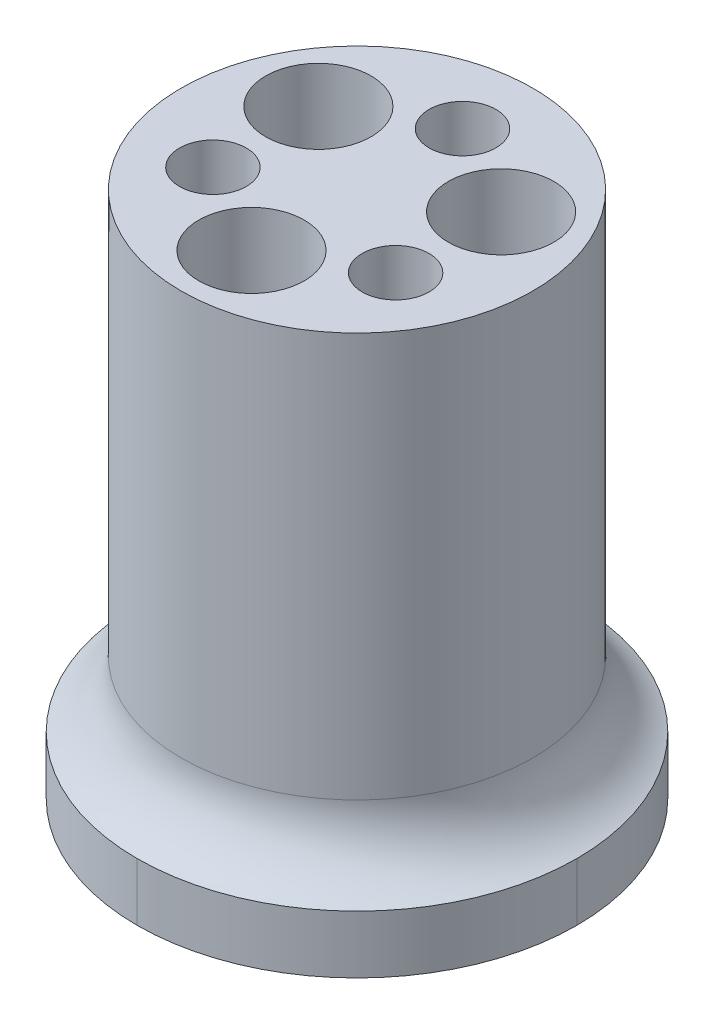
SolidWorks part; units mm, degrees
ref_plane "前视基准面" through (0, 0, 0) normal (0, 0, 1) x (1, 0, 0)
ref_plane "上视基准面" through (0, 0, 0) normal (0, 1, 0) x (1, 0, 0)
ref_plane "右视基准面" through (0, 0, 0) normal (1, 0, 0) x (0, 0, -1)
other "Configuration Table"
sketch "草图1" plane through (0, 0, 0) normal (0, 1, 0) x (1, 0, 0)
  circle A0 centre (0, 0) radius 10
  dimension "D1" = 20
extrude "凸台-拉伸1" add sketch "草图1" along normal blind 30
sketch "草图2" plane through (0, 30, 0) normal (0, 1, 0) x (1, 0, 0)
  circle A0 centre (0, 0) radius 6
  circle A1 centre (0, 6) radius 1.85
  circle A2 centre (5.1962, 3) radius 1.85
  circle A3 centre (5.1962, -3) radius 1.85
  circle A4 centre (0, -6) radius 1.85
  circle A5 centre (-5.1962, -3) radius 1.85
  circle A6 centre (-5.1962, 3) radius 1.85
  point P17 (0, 0)
  dimension "D1" = 12
  dimension "D2" = 3.7
  dimension "D3" = 6
extrude "切除-拉伸1" cut sketch "草图2" against normal through all contours A6 | A1 | A2 | A3 | A4 | A5
sketch "草图3" plane through (0, 30, 0) normal (0, 1, 0) x (1, 0, 0)
  circle A0 centre (0, 6) radius 1.85
  circle A1 centre (-5.1962, -3) radius 1.85
  circle A2 centre (5.1962, -3) radius 1.85
  circle A3 centre (0, 6) radius 1.6
  circle A4 centre (-5.1962, -3) radius 1.6
  circle A5 centre (5.1962, -3) radius 1.6
  dimension "D1" = 3.2
  dimension "D2" = 3.2
  dimension "D3" = 3.2
extrude "凸台-拉伸2" add sketch "草图3" against normal blind 15
sketch "草图4" plane through (0, 0, 0) normal (0, -1, 0) x (1, 0, 0)
  circle A0 centre (-5.1962, 3) radius 1.85
  circle A1 centre (-5.1962, 3) radius 2.5
  circle A2 centre (5.1962, 3) radius 1.85
  circle A3 centre (5.1962, 3) radius 2.5
  circle A4 centre (0, -6) radius 1.85
  circle A5 centre (0, -6) radius 2.5
  dimension "D1" = 5
  dimension "D2" = 5
  dimension "D3" = 5
extrude "切除-拉伸2" cut sketch "草图4" against normal blind 15
sketch "草图5" plane through (0, 0, 0) normal (0, -1, 0) x (1, 0, 0)
  circle A0 centre (0, 6) radius 1.85
  circle A1 centre (-5.1962, -3) radius 1.85
  circle A2 centre (5.1962, -3) radius 1.85
  circle A3 centre (-5.1962, -3) radius 1.6
  circle A4 centre (5.1962, -3) radius 1.6
  circle A5 centre (0, 6) radius 1.6
  dimension "D1" = 3.2
  dimension "D2" = 3.2
  dimension "D3" = 3.2
extrude "凸台-拉伸3" add sketch "草图5" against normal blind 15
sketch "草图6" plane through (0, 30, 0) normal (0, 1, 0) x (1, 0, 0)
  circle A0 centre (-5.1962, 3) radius 2.5
  circle A1 centre (5.1962, 3) radius 2.5
  circle A2 centre (0, -6) radius 2.5
  dimension "D1" = 5
  dimension "D2" = 5
  dimension "D3" = 5
extrude "切除-拉伸4" cut sketch "草图6" against normal blind 15
sketch "草图8" plane through (0, 0, 0) normal (0, -1, 0) x (1, 0, 0)
  line L1 (-12.5, -12.5) -> (12.5, -12.5)
  line L2 (-12.5, -12.5) -> (-12.5, 12.5)
  line L3 (-12.5, 12.5) -> (12.5, 12.5)
  line L4 (12.5, -12.5) -> (12.5, 12.5)
  line L5 (-12.5, -12.5) -> (12.5, 12.5) construction
  line L6 (-12.5, 12.5) -> (12.5, -12.5) construction
  circle A0 centre (0, 0) radius 10
  point P0 (0, 0)
  dimension "D1" = 25
  dimension "D2" = 25
extrude "凸台-拉伸4" add sketch "草图8" against normal blind 3
fillet "圆角1" radius 4 1 edges at (0, 3, -10) type face fillet first side face at (0, 3, -10) second side face at (0, 3, -10)
fillet "圆角6" radius 12.5 1 edges at (12.5, 1.5, 12.5) type face fillet first side face at (12.5, 2.0413, 0.2825) second side face at (-0.2825, 2.0413, 12.5)
fillet "圆角7" radius 12.5 1 edges at (-12.5, 1.5, 12.5) type face fillet first side face at (-5.6305, 1.8876, 12.5) second side face at (-12.5, 2.0413, -0.2825)
fillet "圆角8" radius 12.5 1 edges at (-12.5, 1.5, -12.5) type face fillet first side face at (-12.5, 1.8876, -5.6305) second side face at (0.2825, 2.0413, -12.5)
fillet "圆角9" radius 12.5 1 edges at (12.5, 1.5, -12.5) type face fillet first side face at (5.6305, 1.8876, -12.5) second side face at (12.5, 1.8292, -6.8914)
sketch "草图9" plane through (0, 0, 0) normal (0, -1, 0) x (1, 0, 0)
  circle A0 centre (5.1962, 3) radius 2.5
  circle A1 centre (-5.1962, 3) radius 2.5
  circle A2 centre (0, -6) radius 2.5
extrude "凸台-拉伸6" add sketch "草图9" against normal blind 25
sketch "草图10" plane through (0, 30, 0) normal (0, 1, 0) x (1, 0, 0)
  circle A0 centre (0, 6) radius 1.9
  circle A1 centre (-5.1962, -3) radius 1.9
  circle A2 centre (5.1962, -3) radius 1.9
  dimension "D1" = 3.8
  dimension "D2" = 3.8
  dimension "D3" = 3.8
extrude "切除-拉伸5" cut sketch "草图10" against normal blind 10
sketch "草图11" plane through (0, 30, 0) normal (0, 1, 0) x (1, 0, 0)
  circle A0 centre (-5.1962, 3) radius 3
  circle A1 centre (5.1962, 3) radius 3
  circle A2 centre (0, -6) radius 3
  dimension "D1" = 6
  dimension "D2" = 6
  dimension "D3" = 6
extrude "切除-拉伸6" cut sketch "草图11" against normal blind 15
